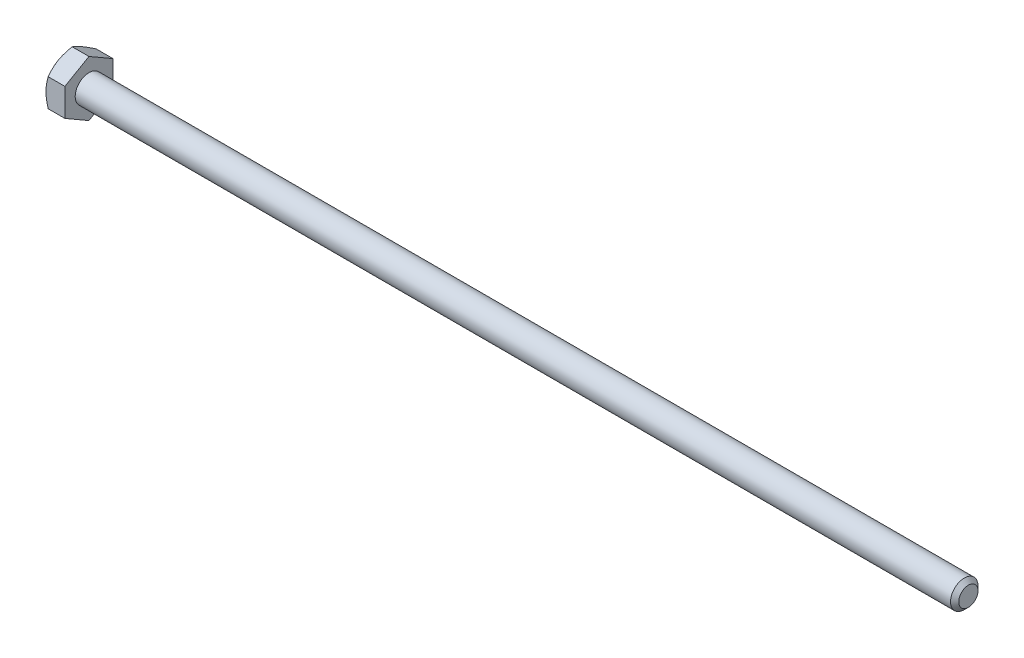
SolidWorks part; units mm, degrees
material "Alloy Steel"
ref_plane "Front Plane" through (0, 0, 0) normal (0, 0, 1) x (1, 0, 0)
ref_plane "Top Plane" through (0, 0, 0) normal (0, 1, 0) x (1, 0, 0)
ref_plane "Right Plane" through (0, 0, 0) normal (1, 0, 0) x (0, 0, -1)
sketch "Sketch1" plane through (0, 0, 0) normal (0, 0, 1) x (1, 0, 0)
  line L0 (-103.7828, 0) -> (103.7828, 0) construction
  line L1 (103.7828, 3.175) -> (103.7828, -3.175) construction
  line L2 (-99.4172, 5.5562) -> (-99.4172, -5.5562) construction
  line L3 (-103.7828, 5.5562) -> (-103.7828, -5.5562) construction
  point P9 (-99.4172, 0)
  point P10 (99.3378, -3.175)
  point P11 (78.3828, 0)
  dimension "D1" = 4.445
ref_plane "Plane2" through (103.7828, 0, 0) normal (1, 0, 0) x (0, 0, -1)
sketch "Sketch5" plane through (103.7828, 0, 0) normal (1, 0, 0) x (0, 0, -1)
  circle A0 centre (0, 0) radius 3.175
extrude "Boss-Extrude3" add sketch "Sketch5" against normal up to vertex (203.2 mm away) up to point (-99.4172, 0, 0)
sketch "Sketch9" [suppressed] plane through (103.7828, 0, 0) normal (1, 0, 0) x (0, 0, -1)
  circle A1 centre (0, 0) radius 3.175
  circle A2 centre (0, 0) radius 3.175
  dimension "D1" = 0
chamfer "Chamfer1" distance 0.9525 angle 45 1 edges at (103.7828, 0, -3.175)
sketch "Sketch11" plane through (0, 0, 0) normal (0, 0, 1) x (1, 0, 0)
  line L0 (-99.4172, 3.175) -> (-99.4172, 0)
  line L1 (-99.4172, 0) -> (81.5578, 0)
  line L3 (81.5578, 0) -> (78.3828, 3.175)
  line L4 (-99.4172, 3.175) -> (78.3828, 3.175)
  dimension "D1" = 45
  dimension "MIn Thread" = 25.4
revolve "Revolve1" add sketch "Sketch11" angle 360 about L1
sketch "Sketch6" plane through (-99.4172, 0, 0) normal (-1, 0, 0) x (0, 0, 1)
  line L0 (0, 5.5562) -> (0, -5.5562) construction
  line L1 (5.5563, 3.2079) -> (0, 6.4158)
  line L2 (0, 6.4158) -> (-5.5562, 3.2079)
  line L3 (-5.5562, 3.2079) -> (-5.5562, -3.2079)
  line L4 (-5.5562, -3.2079) -> (0, -6.4158)
  line L5 (0, -6.4158) -> (5.5563, -3.2079)
  line L6 (5.5563, -3.2079) -> (5.5563, 3.2079)
  circle A0 centre (0, 0) radius 5.5562 construction
extrude "Boss-Extrude4" add sketch "Sketch6" along normal up to vertex (4.3656 mm away) up to point (-103.7828, -5.5562, 0)
sketch "Sketch7" plane through (-103.7828, 0, 0) normal (-1, 0, 0) x (0, 0, 1)
  circle A0 centre (0, 0) radius 5.5562 construction
  circle A1 centre (0, 0) radius 5.5562
sketch "Sketch8" plane through (-103.7828, 0, 0) normal (-1, 0, 0) x (0, 0, 1)
  circle A0 centre (0, 0) radius 5.5562 construction
  circle A1 centre (0, 0) radius 5.5562
extrude "Cut-Extrude3" cut sketch "Sketch8" against normal through all draft 60 flip side to cut
sketch "Sketch12" plane through (-103.7828, 0, 0) normal (-1, 0, 0) x (0, 0, 1)
  line L0 (0, 4.2783) -> (0, 2.3892) construction
  line L1 (0.1667, 4.2783) -> (0.1667, 2.3892)
  line L2 (-0.1667, 4.2783) -> (-0.1667, 2.3892)
  line L3 (0, 3.175) -> (0, -3.175) construction
  arc A0 (0.1667, 4.2783) -> (-0.1667, 4.2783) centre (0, 4.2783) ccw
  arc A1 (-0.1667, 2.3892) -> (0.1667, 2.3892) centre (0, 2.3892) ccw
  circle A3 centre (0, 0) radius 2.2225 construction
  circle A4 centre (0, 0) radius 4.445 construction
  point P2 (0, 3.3337)
  dimension "D1" = 4.445
  dimension "D3" = 8.89
  dimension "D2" = 0.3334
extrude "Cut-Extrude4" cut sketch "Sketch12" against normal blind 0.254
pattern_circular "CirPattern1" count 6 over 360 about axis through (-99.4172, 0, 0) along (1, 0, 0) of "Cut-Extrude4"
ref_plane "Plane3" through (78.3828, 0, 0) normal (1, 0, 0) x (0, 0, -1)
ref_axis "Center Axis1" through (146.542, 0, 0) along (-1, 0, 0)
ref_plane "Contact Plane1" through (78.3828, 0, 0) normal (1, 0, 0) x (0, 0, -1)
ref_plane "Contact Plane2" through (-99.4172, 0, 0) normal (1, 0, 0) x (0, 0, -1)
split "Split1" [suppressed] bodies to split 117
curve "Helix/Spiral1" [suppressed] pitch 1.27 height 26.67 turns 21 parameters "Pitch"=1.27
sketch "Sketch10" [suppressed] plane through (0, 0, 0) normal (0, 0, 1) x (1, 0, 0)
  line L0 (103.7828, 3.175) -> (104.2591, 2.3501)
  line L1 (104.2591, 2.3501) -> (104.4178, 2.3501)
  line L2 (104.4178, 2.3501) -> (104.8941, 3.175)
  line L3 (103.7828, 3.175) -> (104.8941, 3.175)
  line L4 (104.3384, 3.175) -> (104.3384, 2.3501) construction
  line L5 (104.0209, 2.7626) -> (104.6559, 2.7626) construction
  dimension "D1" = 60
  dimension "D2" = 0.1588
  dimension "D3" = 0.635
sweep "Cut-Sweep1" [suppressed] cut profiles "Sketch10" path "Helix/Spiral1"
sketch "Sketch13" [suppressed] plane through (78.3828, 0, 0) normal (1, 0, 0) x (0, 0, -1)
  circle A1 centre (0, 0) radius 3.175
  circle A2 centre (0, 0) radius 3.175
  dimension "D1" = 0
extrude "Boss-Extrude5" [suppressed] add sketch "Sketch13" along normal through all draft 60
equation "\"D2@Sketch10\" = \"Pitch@Helix/Spiral1\"*.125"
equation "\"D3@Sketch10\" = \"Pitch@Helix/Spiral1\"*.5"
equation "\"D3@Helix/Spiral1\"=\"Thread Length@Sketch1\"+\"Pitch@Helix/Spiral1\""
equation "\"D1@Chamfer1\" = \"Pitch@Helix/Spiral1\"*.75"
equation "\"D1@Sketch12\" = \"Hex@Sketch1\"*.4"
equation "\"D3@Sketch12\" = \"Hex@Sketch1\"*.8"
equation "\"D2@Sketch12\" = \"Hex@Sketch1\"*.03"
equation "\"D1@Sketch1\" = \"Pitch@Helix/Spiral1\"*3.5"
